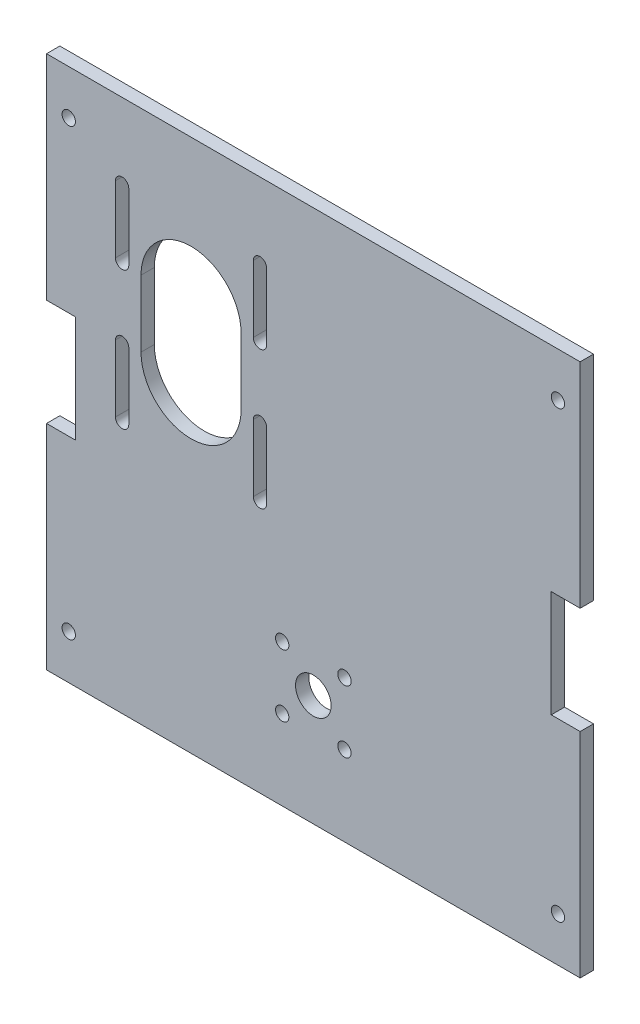
SolidWorks part; units mm, degrees
ref_plane "Plan de face" through (0, 0, 0) normal (0, 0, 1) x (1, 0, 0)
ref_plane "Plan de dessus" through (0, 0, 0) normal (0, 1, 0) x (1, 0, 0)
ref_plane "Plan de droite" through (0, 0, 0) normal (1, 0, 0) x (0, 0, -1)
sketch "Esquisse1" plane through (0, 0, 0) normal (0, 0, 1) x (1, 0, 0)
  line L0 (-27.5, 17.5) -> (-27.5, 32.5) construction
  line L1 (60, -65) -> (-60, -65) construction
  line L3 (60, 65) -> (-60, 65)
  line L4 (-60, -65) -> (-60, -34) construction
  line L5 (60, -65) -> (-60, 65) construction
  line L6 (60, 65) -> (-60, -65) construction
  line L9 (60, -55) -> (50, -55)
  line L10 (50, -65) -> (50, -55) construction
  line L13 (-60, -55) -> (-50, -55)
  line L15 (-38.75, 17.5) -> (-38.75, 32.5)
  line L16 (-16.25, 17.5) -> (-16.25, 32.5)
  line L17 (-43, 33) -> (-43, 48) construction
  line L18 (-44.5, 33) -> (-44.5, 48)
  line L19 (-41.5, 33) -> (-41.5, 48)
  line L20 (-43, 2) -> (-43, 17) construction
  line L21 (-44.5, 2) -> (-44.5, 17)
  line L22 (-41.5, 2) -> (-41.5, 17)
  line L23 (-27.5, 65) -> (-27.5, -65) construction
  line L24 (-27.5, 43.75) -> (-27.5, 6.25) construction
  line L27 (-12, 2) -> (-12, 17) construction
  line L30 (-10.5, 2) -> (-10.5, 17)
  line L31 (-13.5, 2) -> (-13.5, 17)
  line L32 (-12, 33) -> (-12, 48) construction
  line L33 (-10.5, 33) -> (-10.5, 48)
  line L34 (-13.5, 33) -> (-13.5, 48)
  line L35 (-105, -55) -> (-105, 65) construction
  line L36 (-60, -55) -> (-110, -55) construction
  line L44 (0, 65) -> (0, -65) construction
  line L49 (60, 17) -> (53.5, 17)
  line L50 (-55, -65) -> (-55, 65) construction
  line L51 (60, -55) -> (110, -55) construction
  line L52 (-50, -55) -> (50, -55)
  line L54 (60, -25) -> (60, -55)
  line L55 (-60, -25) -> (-50, -25) construction
  line L58 (-50, -25) -> (-50, -65) construction
  line L59 (50, -25) -> (50, -65) construction
  line L60 (60, -25) -> (50, -25) construction
  line L61 (-60, -7) -> (-53.5, -7)
  line L62 (-60, -25) -> (-60, -7)
  line L64 (60, -25) -> (60, -7)
  line L65 (-60, -55) -> (-60, -25)
  line L66 (60, -25) -> (59, -25)
  line L68 (-60, -25) -> (-59, -25)
  line L69 (-60, 17) -> (-53.5, 17)
  line L70 (-53.5, -7) -> (-53.5, 17)
  line L71 (-60, 5) -> (-53.5, 17) construction
  line L72 (-60, 5) -> (-53.5, -7) construction
  line L73 (53.5, -7) -> (53.5, 17)
  line L74 (60, -7) -> (53.5, -7)
  line L76 (60, 17) -> (60, 65)
  line L77 (-60, 17) -> (-60, 65)
  arc A0 (-38.75, 17.5) -> (-16.25, 17.5) centre (-27.5, 17.5) ccw
  arc A1 (-16.25, 32.5) -> (-38.75, 32.5) centre (-27.5, 32.5) ccw
  arc A2 (-44.5, 33) -> (-41.5, 33) centre (-43, 33) ccw
  arc A3 (-41.5, 48) -> (-44.5, 48) centre (-43, 48) ccw
  arc A4 (-44.5, 2) -> (-41.5, 2) centre (-43, 2) ccw
  arc A5 (-41.5, 17) -> (-44.5, 17) centre (-43, 17) ccw
  arc A10 (-10.5, 2) -> (-13.5, 2) centre (-12, 2) cw
  arc A11 (-13.5, 17) -> (-10.5, 17) centre (-12, 17) cw
  arc A12 (-10.5, 33) -> (-13.5, 33) centre (-12, 33) cw
  arc A13 (-13.5, 48) -> (-10.5, 48) centre (-12, 48) cw
  circle A29 centre (-55, -45) radius 1.5
  circle A30 centre (-55, 5) radius 1.5 construction
  circle A31 centre (-55, 55) radius 1.5
  circle A32 centre (55, 55) radius 1.5
  circle A33 centre (55, 5) radius 1.5 construction
  circle A34 centre (55, -45) radius 1.5
  point P0 (0, 0)
  point P14 (-27.5, 25)
  point P21 (-43, 40.5)
  point P28 (-43, 9.5)
  point P37 (-12, 9.5)
  point P44 (-12, 40.5)
  point P51 (-60, 5)
  dimension "D13" = 90
  dimension "D17" = 24
  dimension "D22" = 3
  dimension "D23" = 10
  dimension "D15" = 3
  dimension "D1" = 10
  dimension "D2" = 10
  dimension "D3" = 130
  dimension "D4" = 120
  dimension "D5" = 32.5
  dimension "D6" = 15.5
  dimension "D7" = 22.5
  dimension "D8" = 3
  dimension "D9" = 15.5
  dimension "D10" = 15
  dimension "D11" = 3
  dimension "D12" = 31
  dimension "D14" = 5
  dimension "D16" = 10
  dimension "D18" = 6.5
  dimension "D20" = 50
  dimension "D24" = 10
extrude "Boss.-Extru.1" add sketch "Esquisse1" along normal blind 3
sketch "Esquisse3" plane through (0, 0, 3) normal (0, 0, 1) x (1, 0, 0)
  line L0 (-60, -55) -> (60, -55) construction
  line L4 (0, 65) -> (0, -42) construction
  line L5 (60, 65) -> (-60, 65) construction
  line L6 (-7, -23) -> (7, -23) construction
  line L7 (7, -42) -> (-7, -42) construction
  line L8 (12, -37) -> (12, -23) construction
  line L9 (7, -18) -> (-7, -18) construction
  line L10 (-12, -37) -> (-12, -23) construction
  line L11 (12, -42) -> (-12, -18) construction
  line L12 (12, -18) -> (-12, -42) construction
  line L13 (-7, -23) -> (-7, -37) construction
  circle A0 centre (0, -30) radius 4
  arc A2 (-7, -42) -> (-12, -37) centre (-7, -37) cw construction
  arc A3 (7, -42) -> (12, -37) centre (7, -37) ccw construction
  arc A4 (12, -23) -> (7, -18) centre (7, -23) ccw construction
  arc A5 (-7, -18) -> (-12, -23) centre (-7, -23) ccw construction
  circle A6 centre (-7, -23) radius 1.5
  circle A7 centre (7, -23) radius 1.5
  circle A8 centre (7, -37) radius 1.5
  circle A9 centre (-7, -37) radius 1.5
  dimension "D1" = 8
  dimension "D2" = 25
  dimension "D3" = 14
  dimension "D4" = 5
  dimension "D5" = 3
  dimension "D8" = 14
  dimension "D6" = 2
  dimension "D7" = 2
extrude "Enlèv. mat.-Extru.3" cut sketch "Esquisse3" against normal blind 10
